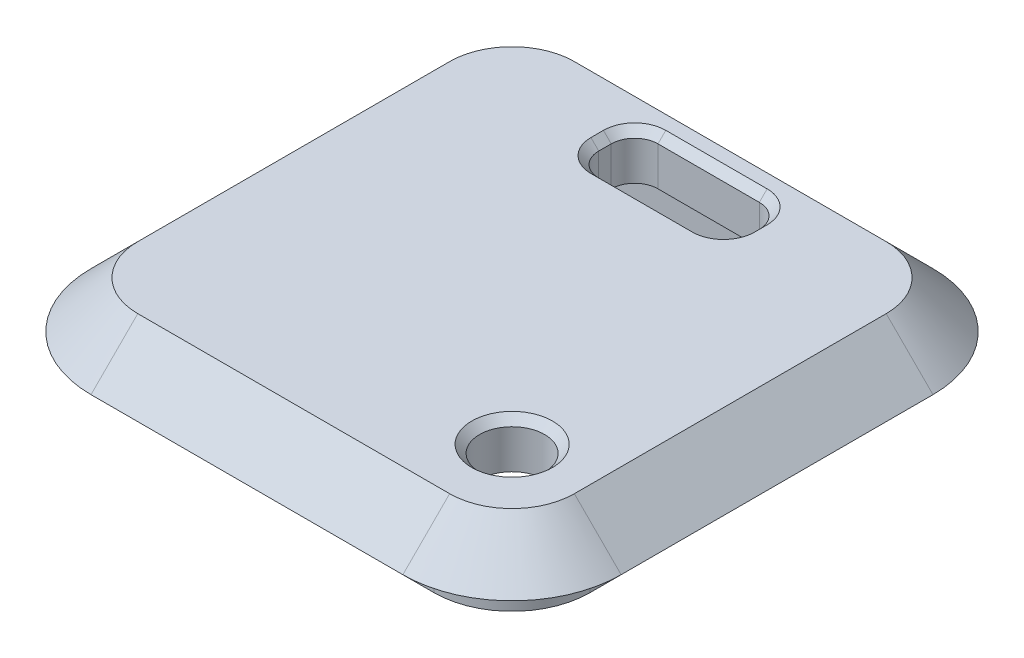
SolidWorks part; units mm, degrees
ref_plane "Alzado" through (0, 0, 0) normal (0, 0, 1) x (1, 0, 0)
ref_plane "Planta" through (0, 0, 0) normal (0, 1, 0) x (1, 0, 0)
ref_plane "Vista lateral" through (0, 0, 0) normal (1, 0, 0) x (0, 0, -1)
sketch "Croquis1" plane through (0, 0, 0) normal (0, 1, 0) x (1, 0, 0)
  line L1 (-17, 17) -> (17, 17)
  line L2 (-17, 17) -> (-17, -17)
  line L3 (-17, -17) -> (17, -17)
  line L4 (17, 17) -> (17, -17)
  line L5 (-17, 17) -> (17, -17) construction
  line L6 (-17, -17) -> (17, 17) construction
  point P0 (0, 0)
  dimension "D1" = 34
  dimension "D2" = 34
extrude "Saliente-Extruir1" add sketch "Croquis1" along normal blind 3
fillet "Redondeo1" radius 7 4 edges at (-17, 1.5, -17) (-17, 1.5, 17) (17, 1.5, -17) (17, 1.5, 17)
chamfer "Chaflán1" distance 3 angle 45 8 edges at (17, 3, 0) (14.9497, 3, -14.9497) (14.9497, 3, 14.9497) (0, 3, -17) (0, 3, 17) (-14.9497, 3, -14.9497) (-14.9497, 3, 14.9497) (-17, 3, 0)
sketch "Croquis2" plane through (0, 3, 0) normal (0, 1, 0) x (1, 0, 0)
  line L3 (-4.75, 12.613) -> (4.75, 12.613)
  line L4 (-4.75, 12.613) -> (-4.75, 8.813)
  line L5 (-4.75, 8.813) -> (4.75, 8.813)
  line L6 (4.75, 12.613) -> (4.75, 8.813)
  line L7 (-4.75, 12.613) -> (4.75, 8.813) construction
  line L8 (-4.75, 8.813) -> (4.75, 12.613) construction
  circle A2 centre (9.26, -9.2522) radius 2.0874
  point P0 (0, 10.713)
  dimension "D2" = 9.5
  dimension "D1" = 3.8
extrude "Cortar-Extruir1" cut sketch "Croquis2" against normal through all
fillet "Redondeo2" radius 1.5 4 edges at (-4.75, 1.5, -8.813) (4.75, 1.5, -8.813) (4.75, 1.5, -12.613) (-4.75, 1.5, -12.613)
chamfer "Chaflán2" distance 0.5 angle 45 9 edges at (4.3107, 3, -12.1736) (4.75, 3, -10.713) (4.3107, 3, -9.2523) (0, 3, -8.813) (-4.3107, 3, -9.2523) (-4.75, 3, -10.713) (-4.3107, 3, -12.1736) (0, 3, -12.613) (9.26, 3, 11.3397)
sketch "Croquis3" plane through (0, 0, 0) normal (0, 0, 1) x (1, 0, 0)
  line L0 (-15.871, -6.0083) -> (-14.471, -5.2)
  line L1 (-17, 0) -> (-10, 0) construction
  line L2 (-14.471, -5.2) -> (-14.471, -3)
  line L3 (-15.871, -6.0083) -> (-13, -8)
  line L4 (-13, -8) -> (-12.471, -3)
  line L5 (-14.471, -3) -> (-15, 0)
  line L6 (-12.471, -3) -> (-13, 0)
  line L7 (-15, 0) -> (-13, 0)
  dimension "D1" = 2
  dimension "D2" = 170
  dimension "D3" = 8
  dimension "D4" = 3
  dimension "D5" = 2
  dimension "D6" = 120
  dimension "D7" = 1.4
  dimension "D8" = 5.2
extrude "Saliente-Extruir2" add sketch "Croquis3" along normal mid plane 10
fillet "Redondeo3" radius 0.2 1 edges at (-13, -8, 0)
fillet "Redondeo4" radius 0.2 1 edges at (-15.871, -6.0083, 0)
fillet "Redondeo5" radius 10 2 edges at (-14.471, -3, 0) (-12.471, -3, 0)
sketch "Croquis4" plane through (0, 0, 0) normal (0, -1, 0) x (1, 0, 0)
  line L0 (-13, 10) -> (-13, -10)
  line L1 (-10, 15) -> (10, 15)
  line L2 (-15, 10) -> (-15, -10)
  line L3 (-10, -15) -> (10, -15)
  line L4 (15, 10) -> (15, -10)
  line L5 (-15, 15) -> (15, -15) construction
  line L6 (-15, -15) -> (15, 15) construction
  line L7 (-10, -13) -> (10, -13)
  line L8 (13, 10) -> (13, -10)
  line L9 (-10, 13) -> (10, 13)
  arc A0 (10, -15) -> (15, -10) centre (10, -10) ccw
  arc A1 (15, 10) -> (10, 15) centre (10, 10) ccw
  arc A2 (-10, 15) -> (-15, 10) centre (-10, 10) ccw
  arc A3 (-15, -10) -> (-10, -15) centre (-10, -10) ccw
  arc A4 (-13, -10) -> (-10, -13) centre (-10, -10) ccw
  arc A5 (10, -13) -> (13, -10) centre (10, -10) ccw
  arc A6 (13, 10) -> (10, 13) centre (10, 10) ccw
  arc A7 (-10, 13) -> (-13, 10) centre (-10, 10) ccw
  point P0 (0, 0)
  dimension "D3" = 5
  dimension "D1" = 30
  dimension "D2" = 30
  dimension "D4" = 2
extrude "Saliente-Extruir3" add sketch "Croquis4" along normal blind 2
